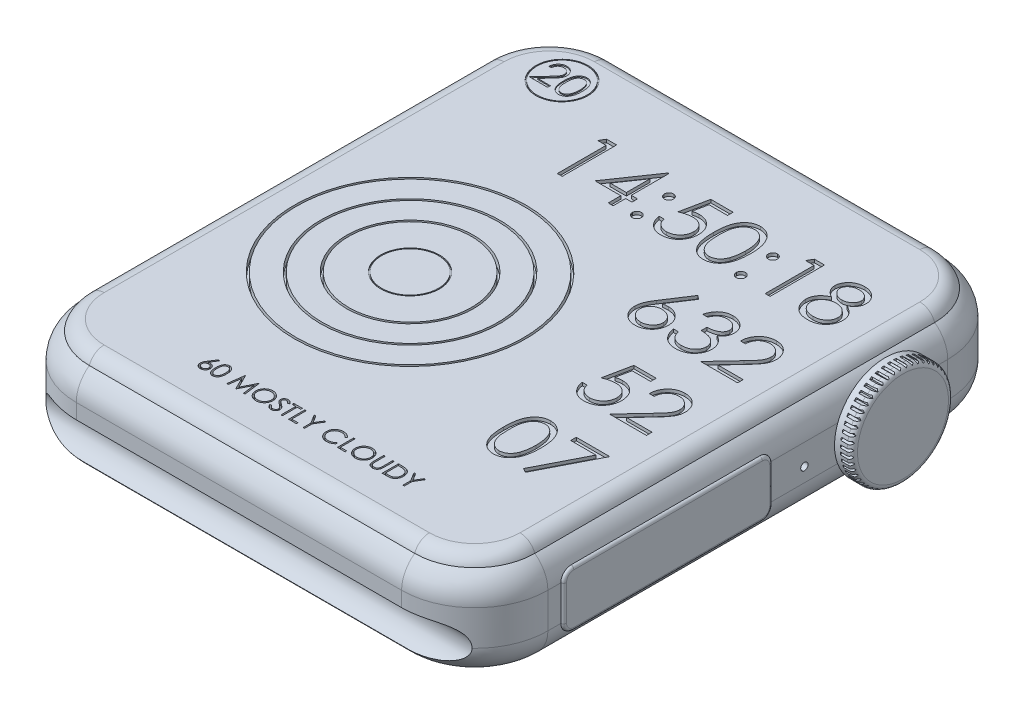
SolidWorks part; units mm, degrees
ref_plane "Front Plane" through (0, 0, 0) normal (0, 0, 1) x (1, 0, 0)
ref_plane "Top Plane" through (0, 0, 0) normal (0, 1, 0) x (1, 0, 0)
ref_plane "Right Plane" through (0, 0, 0) normal (1, 0, 0) x (0, 0, -1)
sketch "Sketch1" plane through (0, 0, 0) normal (0, 1, 0) x (1, 0, 0)
  line L0 (395.4899, 1327.7412) -> (-395.4899, 1327.7412)
  line L1 (-573.2899, 1149.9412) -> (-573.2899, 177.8)
  line L2 (-395.4899, 0) -> (395.4899, 0)
  line L3 (573.2899, 177.8) -> (573.2899, 1149.9412)
  arc A0 (-395.4899, 1327.7412) -> (-573.2899, 1149.9412) centre (-395.4899, 1149.9412) ccw
  arc A1 (573.2899, 1149.9412) -> (395.4899, 1327.7412) centre (395.4899, 1149.9412) ccw
  arc A2 (395.4899, 0) -> (573.2899, 177.8) centre (395.4899, 177.8) ccw
  arc A3 (-573.2899, 177.8) -> (-395.4899, 0) centre (-395.4899, 177.8) ccw
  dimension "D1" = 177.8
extrude "Boss-Extrude1" add sketch "Sketch1" along normal blind 223.52
sketch "Sketch2" plane through (0, 223.52, 0) normal (0, 1, 0) x (1, 0, 0)
  line L0 (-395.4899, 1295.9912) -> (395.4899, 1295.9912)
  line L1 (541.5399, 1149.9412) -> (541.5399, 177.8)
  line L2 (395.4899, 31.75) -> (-395.4899, 31.75)
  line L3 (-541.5399, 1149.9412) -> (-541.5399, 177.8)
  arc A0 (-395.4899, 1295.9912) -> (-541.5399, 1149.9412) centre (-395.4899, 1149.9412) ccw
  arc A1 (541.5399, 1149.9412) -> (395.4899, 1295.9912) centre (395.4899, 1149.9412) ccw
  arc A2 (395.4899, 31.75) -> (541.5399, 177.8) centre (395.4899, 177.8) ccw
  arc A3 (-541.5399, 177.8) -> (-395.4899, 31.75) centre (-395.4899, 177.8) ccw
  dimension "D1" = 292.1
extrude "Boss-Extrude4" add sketch "Sketch2" along normal blind 25.4
fillet "Fillet4" radius 38.1 8 edges at (-498.7629, 248.92, -74.5271) (0, 248.92, -31.75) (498.7629, 248.92, -74.5271) (498.7629, 248.92, -1253.2141) (541.5399, 248.92, -663.8706) (0, 248.92, -1295.9912) (-498.7629, 248.92, -1253.2141) (-541.5399, 248.92, -663.8706)
fillet "Fillet5" radius 76.2 16 edges at (521.2135, 0, -52.0764) (0, 0, 0) (-521.2135, 0, -52.0764) (-521.2135, 0, -1275.6648) (-573.2899, 0, -663.8706) (0, 0, -1327.7412) (521.2135, 0, -1275.6648) (573.2899, 0, -663.8706) (0, 223.52, 0) (521.2135, 223.52, -52.0764) (-521.2135, 223.52, -52.0764) (-573.2899, 223.52, -663.8706) (-521.2135, 223.52, -1275.6648) (0, 223.52, -1327.7412) (521.2135, 223.52, -1275.6648) (573.2899, 223.52, -663.8706)
sketch "Sketch3" plane through (573.2899, 0, 0) normal (1, 0, 0) x (0, 0, -1)
  circle A0 centre (997.9502, 118.2072) radius 123.3606
extrude "Boss-Extrude5" add sketch "Sketch3" along normal blind 43.18
fillet "Fillet6" radius 12.7 1 edges at (616.4699, 118.2072, -1121.3109)
sketch "Sketch4" plane through (0, 248.92, 0) normal (0, 1, 0) x (1, 0, 0)
  line L0 (616.4699, 887.2896) -> (616.4699, 1108.6109) construction
  line L1 (616.4699, 1078.9235) -> (587.7613, 1078.9235)
  line L2 (616.4699, 1078.9235) -> (616.4699, 1073.8603)
  line L3 (616.4699, 1073.8603) -> (587.7613, 1073.8603)
  line L4 (587.7613, 1078.9235) -> (587.7613, 1073.8603)
extrude "Cut-Extrude1" cut sketch "Sketch4" against normal blind 41.148
pattern_circular "CirPattern1" count 51 over 360 about axis through (616.4699, 118.2072, -997.9502) along (-1, 0, 0) of "Cut-Extrude1"
sketch "Sketch5" plane through (573.2899, 0, 0) normal (1, 0, 0) x (0, 0, -1)
  circle A0 centre (801.4328, 110.3548) radius 8.9326
extrude "Cut-Extrude2" cut sketch "Sketch5" against normal blind 80.01
sketch "Sketch6" plane through (573.2899, 0, 0) normal (1, 0, 0) x (0, 0, -1)
  line L0 (882.4839, 161.6279) -> (177.8, 161.6279) construction
  line L5 (234.6132, 187.0279) -> (692.9934, 187.0279)
  line L6 (209.2132, 161.6279) -> (209.2132, 76.2)
  line L7 (234.6132, 50.8) -> (692.9934, 50.8)
  line L8 (718.3934, 161.6279) -> (718.3934, 76.2)
  line L9 (177.8, 76.2) -> (881.9621, 76.2) construction
  arc A0 (234.6132, 187.0279) -> (209.2132, 161.6279) centre (234.6132, 161.6279) ccw
  arc A1 (209.2132, 76.2) -> (234.6132, 50.8) centre (234.6132, 76.2) ccw
  arc A2 (718.3934, 161.6279) -> (692.9934, 187.0279) centre (692.9934, 161.6279) ccw
  arc A3 (692.9934, 50.8) -> (718.3934, 76.2) centre (692.9934, 76.2) ccw
  dimension "D1" = 25.4
extrude "Boss-Extrude6" add sketch "Sketch6" along normal blind 6.35
fillet "Fillet7" radius 7.62 8 edges at (579.6399, 179.5884, -710.9539) (579.6399, 58.2395, -710.9539) (579.6399, 118.9139, -718.3934) (579.6399, 50.8, -463.8033) (579.6399, 58.2395, -216.6527) (579.6399, 118.9139, -209.2132) (579.6399, 179.5884, -216.6527) (579.6399, 187.0279, -463.8033)
sketch "Sketch7" plane through (-573.2899, 0, 0) normal (-1, 0, 0) x (0, 0, 1)
  line L0 (-1121.2203, 90.2974) -> (-938.995, 90.2974) construction
  line L1 (-1121.2203, 99.23) -> (-938.995, 99.23)
  line L2 (-1121.2203, 81.3648) -> (-938.995, 81.3648)
  arc A0 (-1121.2203, 99.23) -> (-1121.2203, 81.3648) centre (-1121.2203, 90.2974) ccw
  arc A1 (-938.995, 81.3648) -> (-938.995, 99.23) centre (-938.995, 90.2974) ccw
  point P2 (-1030.1076, 90.2974)
extrude "Cut-Extrude3" cut sketch "Sketch7" against normal blind 57.15
sketch "Sketch8" plane through (-573.2899, 0, 0) normal (-1, 0, 0) x (0, 0, 1)
  circle A0 centre (-443.1517, 90.2974) radius 11.5468
  circle A1 centre (-402.5052, 90.2974) radius 11.5872
extrude "Cut-Extrude4" cut sketch "Sketch8" against normal blind 104.394
sketch "Sketch9" plane through (-573.2899, 0, 0) normal (-1, 0, 0) x (0, 0, 1)
  line L0 (-1114.5813, 59.8721) -> (-961.1198, 59.8721) construction
  line L3 (-1114.5813, 64.9592) -> (-961.1198, 64.9592)
  line L4 (-1114.5813, 54.7849) -> (-961.1198, 54.7849)
  arc A2 (-1114.5813, 64.9592) -> (-1114.5813, 54.7849) centre (-1114.5813, 59.8721) ccw
  arc A3 (-961.1198, 54.7849) -> (-961.1198, 64.9592) centre (-961.1198, 59.8721) ccw
  point P2 (-1037.8505, 59.8721)
extrude "Cut-Extrude5" cut sketch "Sketch9" against normal blind 104.394
sketch "Sketch10" plane through (-573.2899, 0, 0) normal (-1, 0, 0) x (0, 0, 1)
  line L0 (0, 161.6279) -> (0, 76.2) construction
  circle A0 centre (0, 76.2) radius 48.8793
  arc A1 (-76.2, 0) -> (0, 76.2) centre (-76.2, 76.2) ccw construction
  circle A2 centre (-1327.7412, 76.2) radius 48.8793
extrude "Cut-Extrude6" cut sketch "Sketch10" against normal blind 1651
sketch "Sketch11" plane through (0, 0, 0) normal (0, -1, 0) x (-1, 0, 0)
  circle A0 centre (0, 663.8706) radius 443.1159
extrude "Boss-Extrude7" add sketch "Sketch11" along normal blind 7.62
sketch "Sketch12" plane through (0, -7.62, 0) normal (0, -1, 0) x (-1, 0, 0)
  circle A0 centre (0, 663.8706) radius 427.2571
extrude "Boss-Extrude8" add sketch "Sketch12" along normal blind 7.62
fillet "Fillet8" radius 15.24 1 edges at (0, -15.24, -1091.1277)
fillet "Fillet9" radius 12.7 1 edges at (0, -7.62, -1106.9865)
sketch "Sketch13" plane through (0, -15.24, 0) normal (0, -1, 0) x (-1, 0, 0)
  circle A0 centre (0, 551.7401) radius 54.1983
  circle A1 centre (0, 780.6251) radius 52.393
  circle A5 centre (154.94, 663.8706) radius 71.8982
  circle A6 centre (-162.56, 663.8706) radius 70.0838
  dimension "D1" = 317.5
extrude "Cut-Extrude7" cut sketch "Sketch13" against normal blind 7.62
sketch "Sketch14" plane through (0, 0, 0) normal (0, -1, 0) x (-1, 0, 0)
  line L0 (112.2192, 76.2) -> (-116.3808, 76.2) construction
  line L1 (-395.4899, 76.2) -> (395.4899, 76.2) construction
  line L2 (112.2192, 47.7306) -> (-116.3808, 47.7306)
  line L3 (112.2192, 104.6694) -> (-116.3808, 104.6694)
  line L4 (112.2192, 1251.5412) -> (-116.3808, 1251.5412) construction
  line L5 (395.4899, 1251.5412) -> (-395.4899, 1251.5412) construction
  line L6 (112.2192, 1216.1359) -> (-116.3808, 1216.1359)
  line L7 (112.2192, 1286.9465) -> (-116.3808, 1286.9465)
  arc A0 (112.2192, 47.7306) -> (112.2192, 104.6694) centre (112.2192, 76.2) ccw
  arc A1 (-116.3808, 104.6694) -> (-116.3808, 47.7306) centre (-116.3808, 76.2) ccw
  arc A2 (112.2192, 1216.1359) -> (112.2192, 1286.9465) centre (112.2192, 1251.5412) ccw
  arc A3 (-116.3808, 1286.9465) -> (-116.3808, 1216.1359) centre (-116.3808, 1251.5412) ccw
  point P4 (-2.0808, 76.2)
  point P9 (-2.0808, 1251.5412)
  dimension "D1" = 228.6
extrude "Cut-Extrude-Thin1" cut sketch "Sketch14" against normal blind 17.78 thin thin type one direction wall 5.08
sketch "Sketch15" plane through (0, 248.92, 0) normal (0, 1, 0) x (1, 0, 0)
  text T0 "14:50:18\r\n        632\r\n          52\r\n          07" font "Century Gothic" height in points 500
extrude "Cut-Extrude8" cut sketch "Sketch15" against normal blind 7.62
sketch "Sketch16" plane through (0, 248.92, 0) normal (0, 1, 0) x (1, 0, 0)
  circle A2 centre (-177.2394, 593.3555) radius 276.4935
  circle A3 centre (-177.2394, 593.3555) radius 212.9935
  circle A4 centre (-177.2394, 593.3555) radius 149.4935
  dimension "D1" = 63.5
  dimension "D2" = 63.5
extrude "Cut-Extrude-Thin2" cut sketch "Sketch16" against normal blind 17.78 thin contours A2 | A3 | A4 thin type one direction wall 5.08
sketch "Sketch18" plane through (0, 248.92, 0) normal (0, 1, 0) x (1, 0, 0)
  text T0 "60 MOSTLY CLOUDY" font "Century Gothic" height in points 150
extrude "Cut-Extrude9" cut sketch "Sketch18" against normal blind 12.7
sketch "Sketch19" plane through (0, 248.92, 0) normal (0, 1, 0) x (1, 0, 0)
  text T0 "20" font "Century Gothic" height in points 250
extrude "Cut-Extrude10" cut sketch "Sketch19" against normal blind 2.54
sketch "Sketch20" plane through (0, 248.92, 0) normal (0, 1, 0) x (1, 0, 0)
  circle A0 centre (-395.4899, 1180.953) radius 60.9598
extrude "Cut-Extrude-Thin4" cut sketch "Sketch20" against normal blind 2.54 thin thin type one direction wall 2.54
sketch "Sketch21" plane through (0, 248.92, 0) normal (0, 1, 0) x (1, 0, 0)
  circle A0 centre (-177.2394, 593.3555) radius 69.0138
extrude "Cut-Extrude-Thin5" cut sketch "Sketch21" against normal blind 2.54 thin thin type one direction wall 2.54
